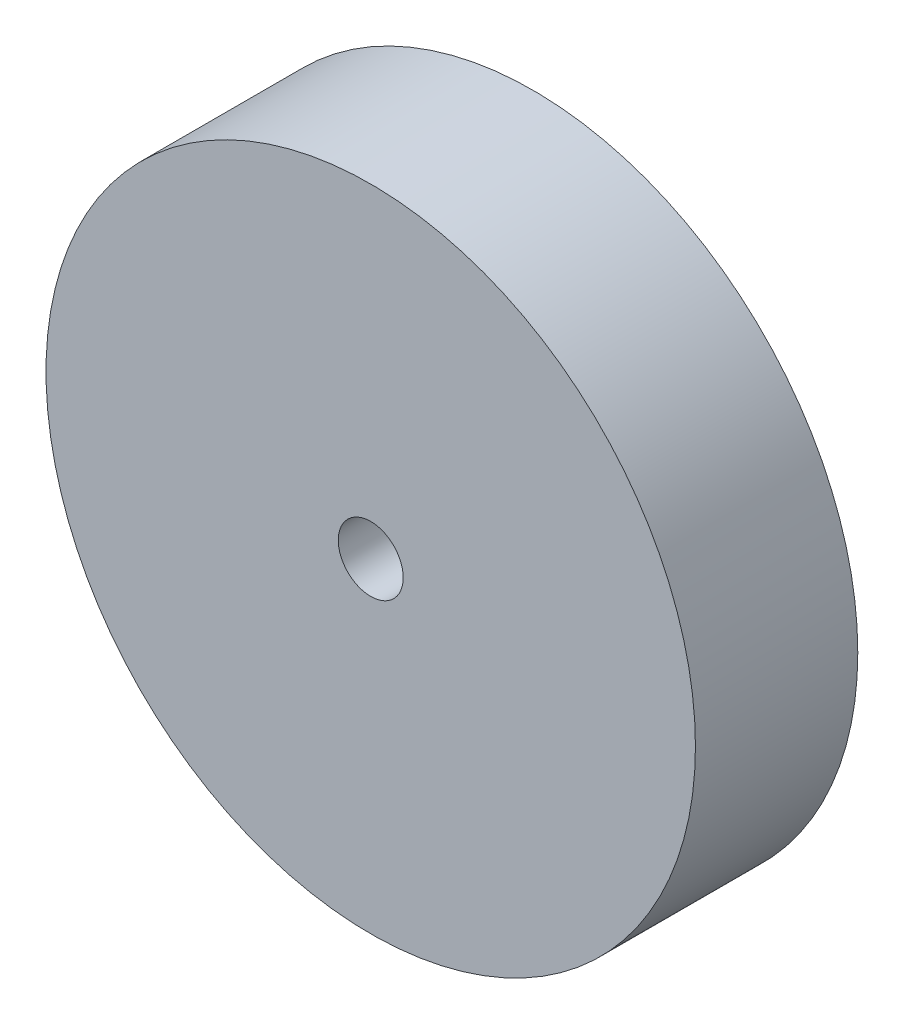
SolidWorks part; units mm, degrees
ref_plane "前视基准面" through (0, 0, 0) normal (0, 0, 1) x (1, 0, 0)
ref_plane "上视基准面" through (0, 0, 0) normal (0, 1, 0) x (1, 0, 0)
ref_plane "右视基准面" through (0, 0, 0) normal (1, 0, 0) x (0, 0, -1)
other "Configuration Table"
sketch "Sketch1" plane through (0, 0, 0) normal (0, 0, 1) x (1, 0, 0)
  circle A0 centre (0, 0) radius 100
extrude "Boss-Extrude1" add sketch "Sketch1" along normal blind 50
sketch "Sketch2" plane through (0, 0, 0) normal (0, 0, 1) x (1, 0, 0)
  circle A0 centre (0, 0) radius 10
extrude "Cut-Extrude1" cut sketch "Sketch2" along normal blind 50
ref_plane "base_bottom_face" through (0, 0, 0) normal (0, 0, 1) x (1, 0, 0)
ref_plane "base_top_face" through (0, 0, 50) normal (0, 0, 1) x (1, 0, 0)
sketch3d "3DSketch1"
  line L0 (0, 0, 0) -> (0, 0, 50) construction
ref_axis "axis_1_rot" through (0, 0, 0) along (0, 0, 1)
